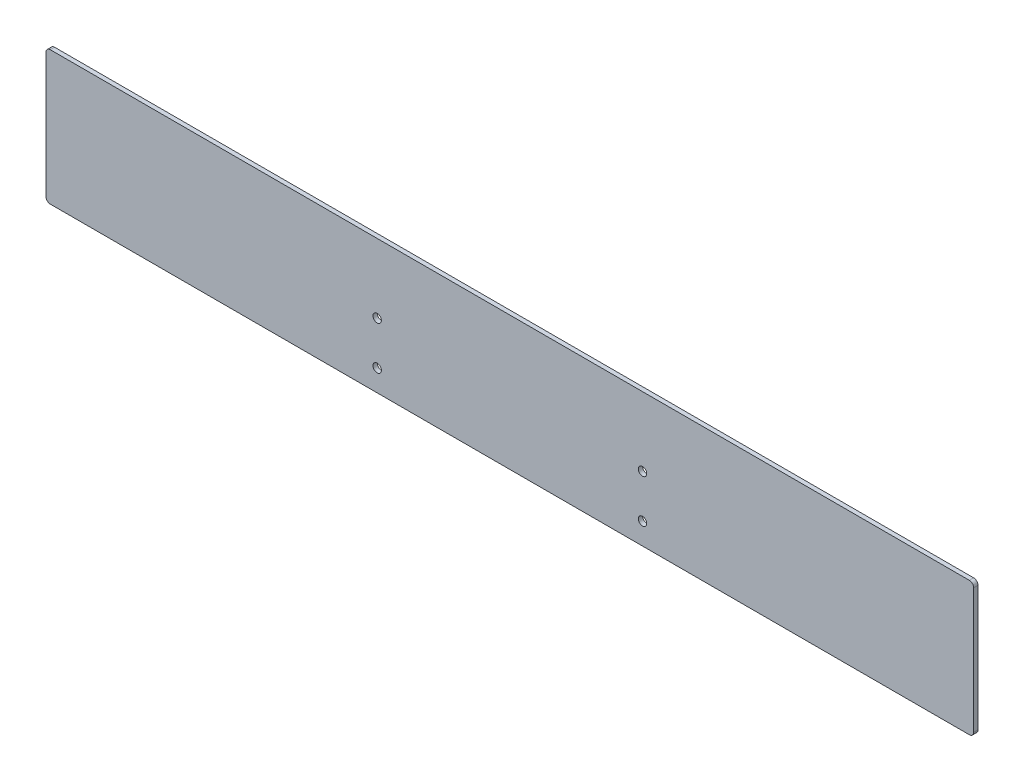
SolidWorks part; units mm, degrees
ref_plane "Front Plane" through (0, 0, 0) normal (0, 0, 1) x (1, 0, 0)
ref_plane "Top Plane" through (0, 0, 0) normal (0, 1, 0) x (1, 0, 0)
ref_plane "Right Plane" through (0, 0, 0) normal (1, 0, 0) x (0, 0, -1)
sketch "Sketch1" plane through (0, 0, 0) normal (0, 0, 1) x (1, 0, 0)
  line L1 (-356.9059, 17.7035) -> (73.0941, 17.7035)
  line L2 (-356.9059, 17.7035) -> (-356.9059, -44.2965)
  line L3 (-356.9059, -44.2965) -> (73.0941, -44.2965)
  line L4 (73.0941, 17.7035) -> (73.0941, -44.2965)
  circle A0 centre (-80.4059, -14.2965) radius 1.95
  circle A1 centre (-80.4059, -34.2965) radius 1.95
  circle A2 centre (-203.4059, -14.2965) radius 1.95
  circle A3 centre (-203.4059, -34.2965) radius 1.95
  dimension "D3" = 123
  dimension "D4" = 20
  dimension "D1" = 430
  dimension "D2" = 62
  dimension "D5" = 10
  dimension "D6" = 153.5
extrude "Boss-Extrude1" add sketch "Sketch1" along normal blind 2
fillet "Fillet1" radius 2 4 edges at (73.0941, 17.7035, 1) (73.0941, -44.2965, 1) (-356.9059, -44.2965, 1) (-356.9059, 17.7035, 1)
